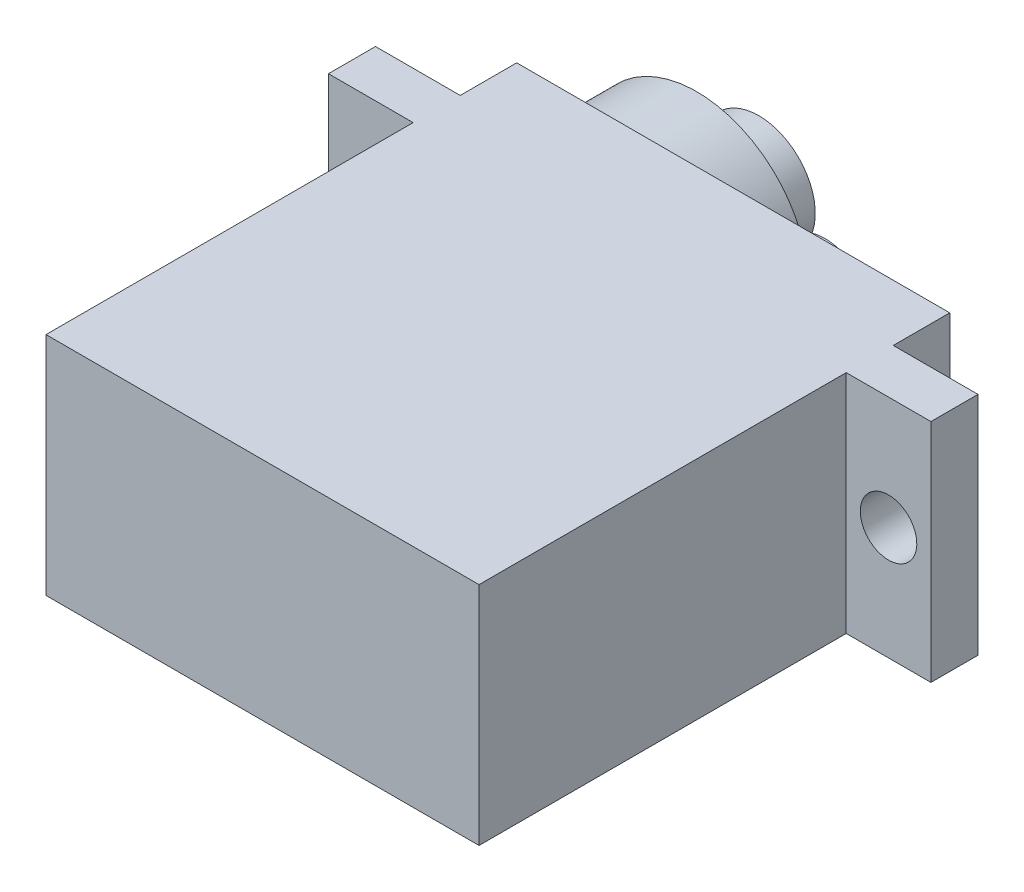
SolidWorks part; units mm, degrees
ref_plane "Front Plane" through (0, 0, 0) normal (0, 0, 1) x (1, 0, 0)
ref_plane "Top Plane" through (0, 0, 0) normal (0, 1, 0) x (1, 0, 0)
ref_plane "Right Plane" through (0, 0, 0) normal (1, 0, 0) x (0, 0, -1)
sketch "Sketch1" plane through (0, 0, 0) normal (0, 0, 1) x (1, 0, 0)
  line L1 (11.5, -6) -> (-11.5, -6)
  line L2 (11.5, -6) -> (11.5, 6)
  line L3 (11.5, 6) -> (-11.5, 6)
  line L4 (-11.5, -6) -> (-11.5, 6)
  line L5 (11.5, -6) -> (-11.5, 6) construction
  line L6 (11.5, 6) -> (-11.5, -6) construction
  point P0 (0, 0)
  dimension "D1" = 23
  dimension "D2" = 12
extrude "Boss-Extrude1" add sketch "Sketch1" along normal blind 25
sketch "Sketch3" plane through (11.5, 0, 0) normal (1, 0, 0) x (0, 0, -1)
  line L0 (-25, 6) -> (0, 6) construction
  line L1 (-3, 6) -> (-5.5, 6)
  line L2 (-3, 6) -> (-3, -6)
  line L3 (-3, -6) -> (-5.5, -6)
  line L4 (-5.5, 6) -> (-5.5, -6)
  line L5 (-25, -6) -> (0, -6) construction
  dimension "D1" = 2.5
  dimension "D2" = 19.5
extrude "Boss-Extrude2" add sketch "Sketch3" along normal blind 4.5
sketch "Sketch4" plane through (-11.5, 0, 0) normal (-1, 0, 0) x (0, 0, 1)
  line L0 (25, 6) -> (0, 6) construction
  line L1 (5.5, 6) -> (3, 6)
  line L2 (5.5, 6) -> (5.5, -6)
  line L3 (5.5, -6) -> (3, -6)
  line L4 (3, 6) -> (3, -6)
  line L5 (25, -6) -> (0, -6) construction
  dimension "D1" = 19.5
  dimension "D2" = 2.5
extrude "Boss-Extrude3" add sketch "Sketch4" along normal blind 4.5
sketch "Sketch5" plane through (0, 0, 0) normal (0, 0, -1) x (-1, 0, 0)
  circle A0 centre (5.443, 0) radius 5.9554
  circle A1 centre (-1.3696, 0.1346) radius 2.4728
  circle A2 centre (5.443, 0) radius 1.9661
extrude "Boss-Extrude13" add sketch "Sketch5" along normal blind 3.5 contours A0 A1 | A1 A0 A2 | A0 A1 | A2 region at (-6.4405, -5.7029, 0) region at (-0.2288, 0.103, 0) region at (1.904, 0.1452, 0) region at (-5.443, 0, 0)
sketch "Sketch7" plane through (0, 0, -3.5) normal (0, 0, -1) x (-1, 0, 0)
  circle A0 centre (5.6429, 0) radius 3
extrude "Boss-Extrude14" add sketch "Sketch7" along normal blind 3.5
sketch "Sketch8" plane through (0, 0, 3) normal (0, 0, -1) x (-1, 0, 0)
  line L4 (13.75, 6) -> (13.75, -7.1508) construction
  line L5 (16, 6) -> (11.5, 6) construction
  line L6 (11.3984, 0) -> (16.9242, 0) construction
  line L9 (-13.75, 6) -> (-13.75, -6.9765) construction
  line L10 (-16, 6) -> (-11.5, 6) construction
  line L13 (-16, -6) -> (-11.5, -6) construction
  arc A1 (-0.1588, -2.0215) -> (-0.0746, 2.2413) centre (5.443, 0) ccw construction
  arc A2 (-0.1588, -2.0215) -> (-0.0746, 2.2413) centre (5.443, 0) ccw construction
  circle A3 centre (13.75, 0) radius 1.5
  circle A4 centre (-13.75, 0) radius 1.5
  dimension "D1" = 6
  dimension "D2" = 3
  dimension "D3" = 3
extrude "Cut-Extrude1" cut sketch "Sketch8" against normal blind 3.5 contours A3 | A4 region at (-13.75, 0, 3)
sketch "Sketch9" plane through (0, -6, 0) normal (0, -1, 0) x (-1, 0, 0)
  line L0 (-8.3308, -10.3562) -> (9.0948, -10.3562) construction
  text T0 "<b>Servo-Motor</b>" font "Century Gothic" height 3.5
extrude "Cut-Extrude2" cut sketch "Sketch9" against normal blind 3.5
sketch "Sketch10" plane through (0, -6, 0) normal (0, -1, 0) x (-1, 0, 0)
  line L0 (-10.0608, -19.0138) -> (10.0778, -19.0138) construction
  text T0 "Team:<b> C1</b>" font "Century Gothic" height 3.5
extrude "Cut-Extrude3" cut sketch "Sketch10" against normal blind 3.5
